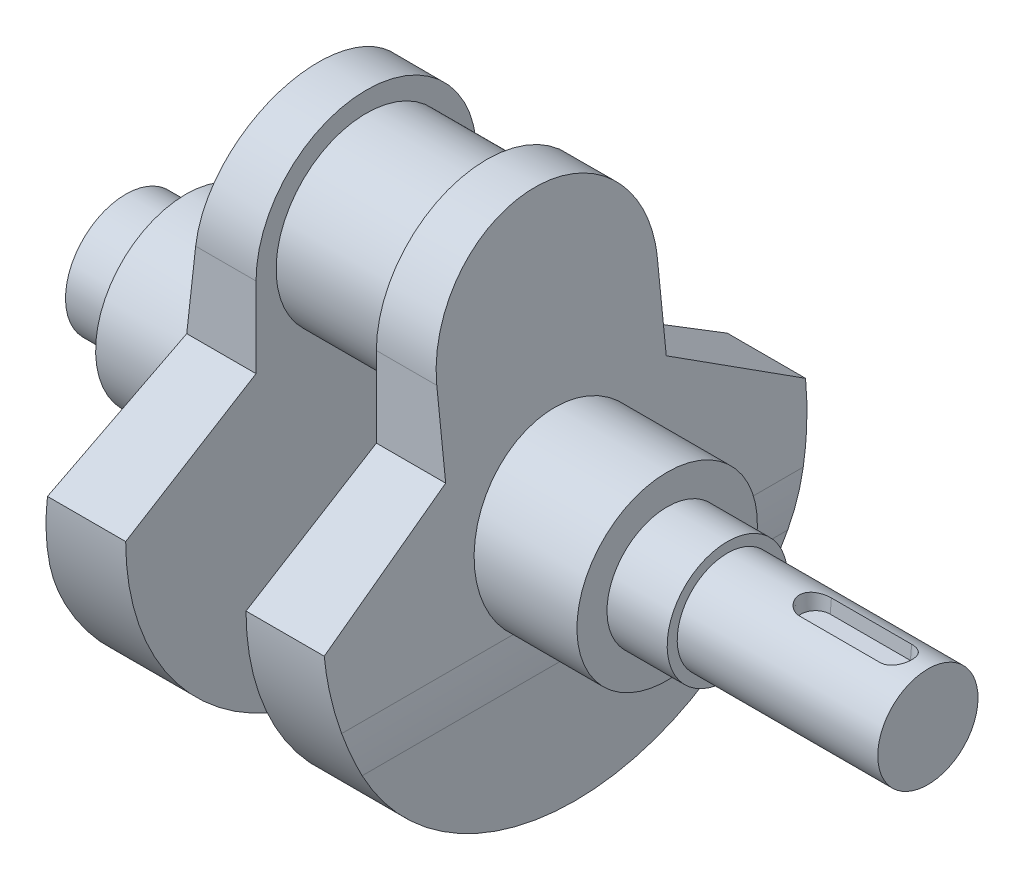
SolidWorks part; units mm, degrees
material "Gray Cast Iron"
ref_plane "Front Plane" through (0, 0, 0) normal (0, 0, 1) x (1, 0, 0)
ref_plane "Top Plane" through (0, 0, 0) normal (0, 1, 0) x (1, 0, 0)
ref_plane "Right Plane" through (0, 0, 0) normal (1, 0, 0) x (0, 0, -1)
sketch "Sketch2" plane through (0, 0, 0) normal (1, 0, 0) x (0, 0, -1)
  circle A0 centre (0, 0) radius 22.5
  dimension "D1" = 45
extrude "Boss-Extrude1" add sketch "Sketch2" along normal blind 15
sketch "Sketch3" plane through (15, 0, 0) normal (1, 0, 0) x (0, 0, -1)
  line L0 (-27.5, 0) -> (-27.5, -20)
  line L1 (-27.5, -20) -> (-60, -40)
  line L2 (0, -69.0647) -> (0, 39.4243) construction
  line L3 (27.5, -20) -> (60, -40)
  line L4 (27.5, 0) -> (27.5, -20)
  arc A0 (27.5, 0) -> (-27.5, 0) centre (0, 0) ccw
  arc A1 (-60, -40) -> (60, -40) centre (0, -40) ccw
  dimension "D1" = 120
  dimension "D3" = 55
  dimension "D2" = 40
  dimension "D4" = 20
  dimension "D5" = 40
extrude "Boss-Extrude2" add sketch "Sketch3" along normal blind 22
sketch "Sketch6" plane through (0, 0, 0) normal (0, 0, 1) x (1, 0, 0)
  line L0 (37, 27.5) -> (27, 27.5)
  line L1 (37, 27.5) -> (15, 27.5) construction
  line L2 (27, 27.5) -> (37, -62.5)
  line L3 (37, -100) -> (37, -40) construction
  line L4 (37, -62.5) -> (37, 27.5)
  dimension "D1" = 10
  dimension "D2" = 90
extrude "Cut-Extrude1" cut sketch "Sketch6" against normal through all both and the other way through all
fillet "Fillet1" radius 100 1 edges at (37, -62.5, 0)
sketch "Sketch8" plane through (0, 0, 0) normal (0, 0, 1) x (1, 0, 0)
  line L0 (37, -100) -> (37, 0) construction
  line L1 (37, -100) -> (37, -68.0385) construction
  line L2 (37, 0) -> (-8.9258, 0) construction
  line L3 (32, -17.5) -> (60, -17.5)
  line L4 (60, -17.5) -> (60, -25)
  line L5 (60, -25) -> (75, -25)
  line L6 (75, -25) -> (75, -27.5)
  line L7 (75, -27.5) -> (125, -27.5)
  line L8 (125, -27.5) -> (125, -40)
  line L9 (125, -40) -> (32, -40)
  line L10 (32, -40) -> (32, -17.5)
  line L11 (32, -40) -> (0.724, -40) construction
  line L12 (32.2778, -20) -> (30.0556, 0) construction
  dimension "D1" = 40
  dimension "D2" = 45
  dimension "D3" = 30
  dimension "D4" = 25
  dimension "D5" = 60
  dimension "D6" = 50
  dimension "D7" = 15
revolve "Revolve1" add sketch "Sketch8" angle 360 about L9
sketch "Sketch9" plane through (0, 0, 0) normal (0, 1, 0) x (1, 0, 0)
  line L0 (125, 0) -> (81.1822, 0) construction
  line L1 (125, -12.5) -> (125, 12.5) construction
  line L2 (117, 0) -> (97, 0) construction
  line L3 (117, -4) -> (97, -4)
  line L4 (117, 4) -> (97, 4)
  arc A0 (117, -4) -> (117, 4) centre (117, 0) ccw
  arc A1 (97, 4) -> (97, -4) centre (97, 0) ccw
  point P7 (107, 0)
  dimension "D2" = 4
  dimension "D1" = 20
  dimension "D3" = 8
extrude "Cut-Extrude2" cut sketch "Sketch9" against normal blind 4 draft 5 and the other way through all from offset 27.5 offset against normal yes
mirror "Mirror1" about plane through (0, 0, 0) normal (1, 0, 0) of bodies 105
sketch "Sketch10" plane through (0, 0, 0) normal (0, 0, 1) x (1, 0, 0)
  line L0 (-75, -74.4184) -> (-75, 5.3043)
extrude "Cut-Extrude3" cut sketch "Sketch10" against normal through all and the other way through all
